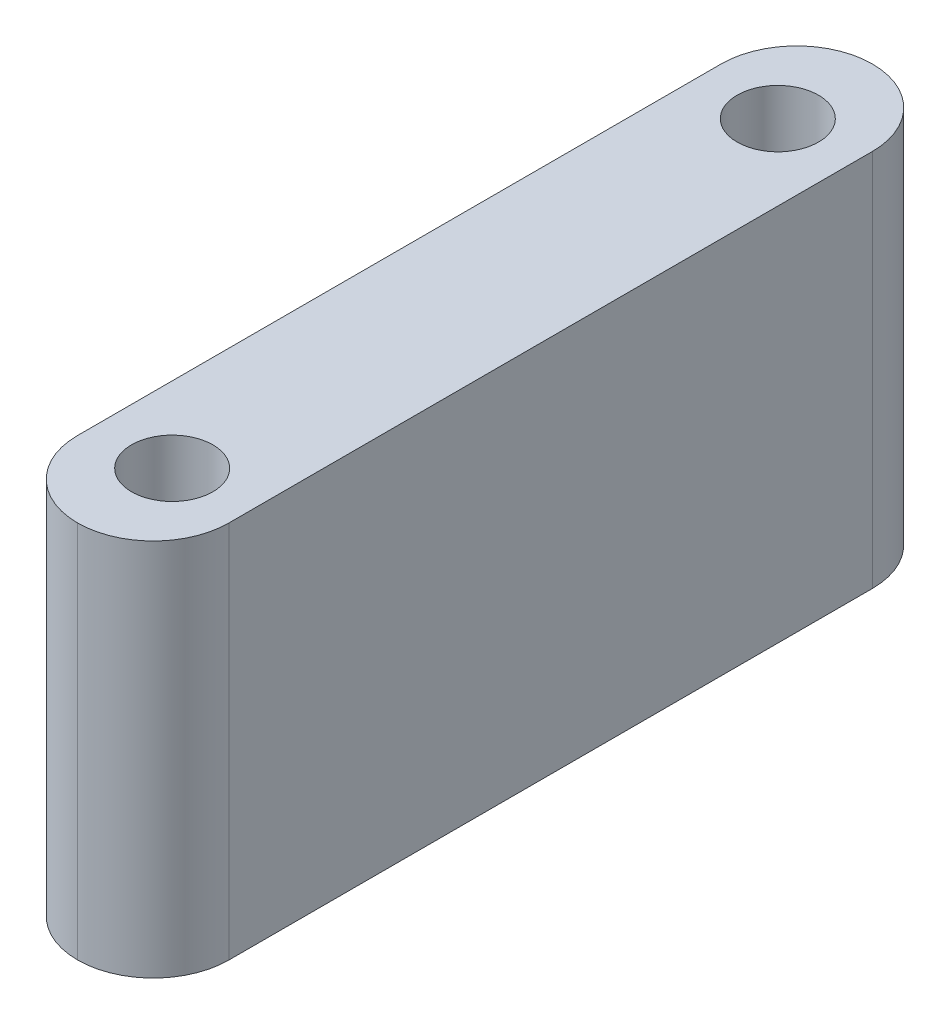
SolidWorks part; units mm, degrees
ref_plane "Front Plane" through (0, 0, 0) normal (0, 0, 1) x (1, 0, 0)
ref_plane "Top Plane" through (0, 0, 0) normal (0, 1, 0) x (1, 0, 0)
ref_plane "Right Plane" through (0, 0, 0) normal (1, 0, 0) x (0, 0, -1)
sketch "Sketch1" plane through (0, 0, 0) normal (0, 1, 0) x (1, 0, 0)
  line L0 (0, 21) -> (-8, 21) construction
  line L1 (0, 0) -> (-8, 0)
  line L2 (0, 0) -> (0, 42)
  line L3 (0, 42) -> (-8, 42)
  line L4 (-8, 0) -> (-8, 42)
  circle A0 centre (-4, 37) radius 2.15
  circle A1 centre (-4, 5) radius 2.15
  point P9 (0, 0)
  point P10 (-4, 21)
  dimension "D3" = 4.3
  dimension "D4" = 32
  dimension "D1" = 42
  dimension "D2" = 8
extrude "Boss-Extrude1" add sketch "Sketch1" along normal blind 20
fillet "Fillet1" radius 4 4 edges at (0, 10, 0) (-8, 10, -42) (0, 10, -42) (-8, 10, 0)
